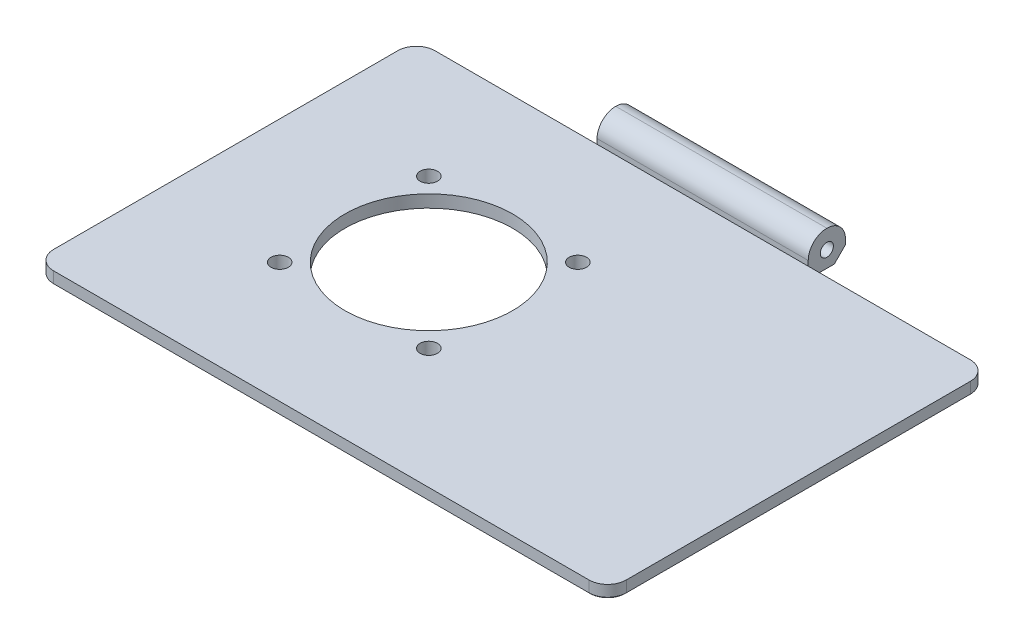
SolidWorks part; units mm, degrees
ref_plane "前视基准面" through (0, 0, 0) normal (0, 0, 1) x (1, 0, 0)
ref_plane "上视基准面" through (0, 0, 0) normal (0, 1, 0) x (1, 0, 0)
ref_plane "右视基准面" through (0, 0, 0) normal (1, 0, 0) x (0, 0, -1)
other "Configuration Table"
sketch "草图1" plane through (0, 0, 0) normal (0, 1, 0) x (1, 0, 0)
  line L1 (3, 0) -> (89.2, 0)
  line L2 (0, 3) -> (0, 58.4)
  line L3 (3, 61.4) -> (89.2, 61.4)
  line L4 (92.2, 3) -> (92.2, 58.4)
  arc A0 (89.2, 61.4) -> (92.2, 58.4) centre (89.2, 58.4) cw
  arc A1 (89.2, 0) -> (92.2, 3) centre (89.2, 3) ccw
  arc A2 (3, 0) -> (0, 3) centre (3, 3) cw
  arc A3 (0, 58.4) -> (3, 61.4) centre (3, 58.4) cw
  point P7 (92.2, 61.4)
  point P10 (92.2, 0)
  point P13 (0, 0)
  dimension "D3" = 3
  dimension "D1" = 92.2
  dimension "D2" = 61.4
extrude "凸台-拉伸1" add sketch "草图1" along normal blind 2
sketch "草图2" plane through (0, 0, 0) normal (0, -1, 0) x (-1, 0, 0)
  line L0 (-89.2, 61.4) -> (-3, 61.4) construction
  line L1 (-29.1, 67.4) -> (-63.1, 67.4)
  line L2 (-29.1, 67.4) -> (-29.1, 61.4)
  line L3 (-29.1, 61.4) -> (-63.1, 61.4)
  line L4 (-63.1, 67.4) -> (-63.1, 61.4)
  point P7 (-46.1, 67.4)
  point P8 (-46.1, 61.4)
  dimension "D1" = 34
  dimension "D2" = 6
  dimension "D3" = 0
extrude "凸台-拉伸2" add sketch "草图2" against normal blind 5.8
sketch "草图3" plane through (63.1, 0, 0) normal (1, 0, 0) x (0, 0, -1)
  line L0 (67.4, 5.8) -> (67.4, 0) construction
  line L1 (67.4, 5.8) -> (61.4, 5.8) construction
  circle A0 centre (64.4, 2.8) radius 1.05
  point P3 (0, 0)
  dimension "D1" = 3
  dimension "D2" = 3
extrude "切除-拉伸1" cut sketch "草图3" against normal through all
fillet "圆角1" radius 3 2 edges at (46.1, 5.8, -67.4) (46.1, 5.8, -61.4)
chamfer "倒角1" distance 2 angle 45 1 edges at (46.1, 0, -67.4)
sketch "草图4" plane through (0, 2, 0) normal (0, 1, 0) x (1, 0, 0)
  line L0 (29.1, 61.4) -> (3, 61.4) construction
  line L1 (0, 58.4) -> (0, 3) construction
  circle A0 centre (20, 43.4) radius 1.4
  circle A1 centre (44, 43.4) radius 1.4
  circle A2 centre (44, 19.4) radius 1.4
  circle A3 centre (20, 19.4) radius 1.4
  circle A4 centre (32, 31.4) radius 13.5
  dimension "D1" = 2.8
  dimension "D2" = 18
  dimension "D3" = 20
  dimension "D6" = 12
  dimension "D7" = 12
  dimension "D8" = 27
  dimension "D4" = 2
  dimension "D5" = 2
extrude "切除-拉伸2" cut sketch "草图4" against normal blind 2
chamfer "倒角2" distance 0.2 angle 45 11 edges at (29.1, 0, -63.4) (63.1, 0, -63.4) (16.05, 0, -61.4) (0.8787, 0, -60.5213) (0, 0, -30.7) (0.8787, 0, -0.8787) (46.1, 0, 0) (76.15, 0, -61.4) (91.3213, 0, -0.8787) (91.3213, 0, -60.5213) (92.2, 0, -30.7)
